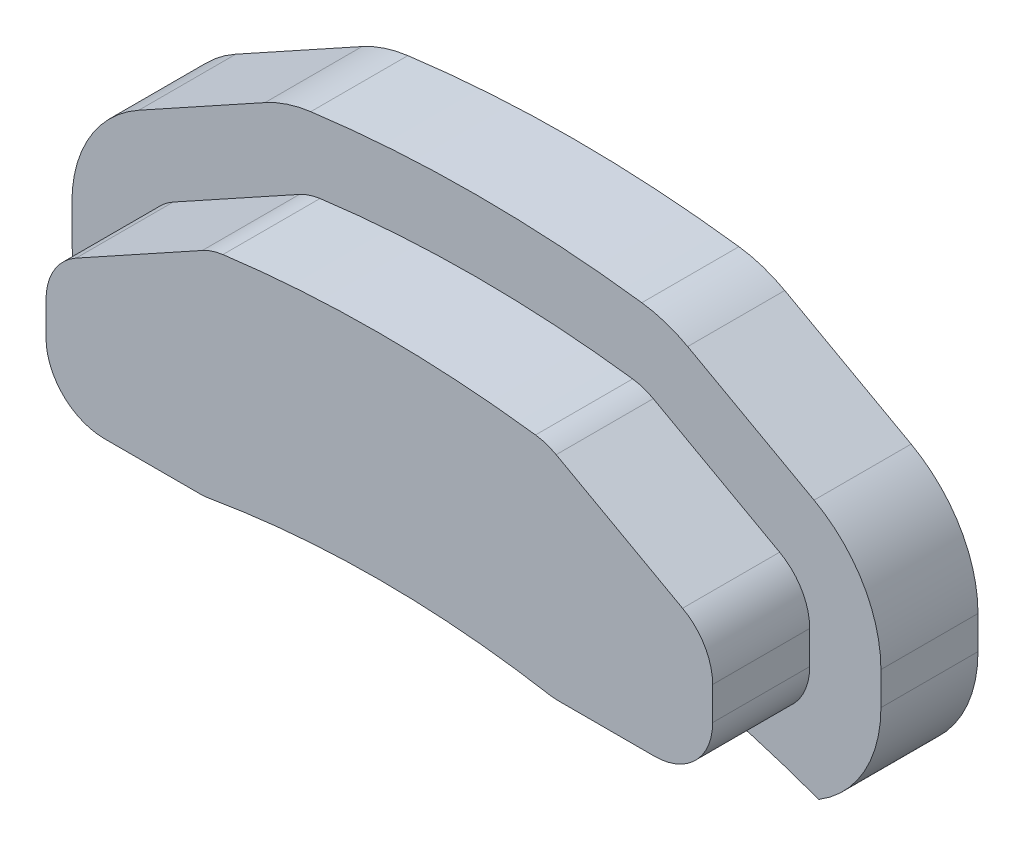
SolidWorks part; units mm, degrees
ref_plane "Front Plane" through (0, 0, 0) normal (0, 0, 1) x (1, 0, 0)
ref_plane "Top Plane" through (0, 0, 0) normal (0, 1, 0) x (1, 0, 0)
ref_plane "Right Plane" through (0, 0, 0) normal (1, 0, 0) x (0, 0, -1)
sketch "Sketch1" plane through (0, 0, 0) normal (0, 0, 1) x (1, 0, 0)
  line L0 (-5.4758, 36.7504) -> (-9.377, 34.5954)
  line L3 (-10.3066, 32) -> (-10.3066, 33.0198)
  line L8 (-5.5524, 30.2) -> (-8.5066, 30.2)
  line L9 (5.5342, 30.2) -> (8.4935, 30.2)
  line L10 (10.2935, 32) -> (10.2935, 33.0198)
  line L11 (5.4587, 36.7526) -> (9.3639, 34.5954)
  arc A0 (-9.377, 34.5954) -> (-10.3066, 33.0198) centre (-8.5066, 33.0198) ccw
  arc A17 (-8.5066, 30.2) -> (-10.3066, 32) centre (-8.5066, 32) cw
  arc A18 (-5.5524, 30.2) -> (-5.2457, 30.2263) centre (-5.5524, 32) ccw
  arc A19 (-5.2457, 30.2263) -> (-0.0091, 30.675) centre (-0.0182, 0) cw
  arc A20 (5.2274, 30.2263) -> (-0.0091, 30.675) centre (0, 0) ccw
  arc A21 (5.5342, 30.2) -> (5.2274, 30.2263) centre (5.5342, 32) cw
  arc A22 (8.4935, 30.2) -> (10.2935, 32) centre (8.4935, 32) ccw
  arc A23 (10.2935, 33.0198) -> (9.3639, 34.5954) centre (8.4935, 33.0198) ccw
  arc A24 (5.4587, 36.7526) -> (4.8212, 36.9619) centre (4.5884, 35.177) ccw
  arc A25 (4.8212, 36.9619) -> (-4.8392, 36.9595) centre (0, 0) ccw
  arc A26 (-4.8392, 36.9595) -> (-5.4758, 36.7504) centre (-4.6055, 35.1748) ccw
  point P0 (0, 0)
  point P1 (6.3862, 36.9268)
  point P3 (-5.1933, 30.0292)
  point P4 (-6.3862, 36.9268)
  point P12 (0, 0)
  point P13 (5.1933, 30.0292)
extrude "Boss-Extrude1" add sketch "Sketch1" along normal blind 5 contours A25 A26 L0 A0 L3 A17 L8 A18 A19 A20 A21 L9 A22 L10 A23 L11 A24 region at (-0.0063, 33.4615, 0)
sketch "Sketch2" plane through (0, 0, 0) normal (0, 0, -1) x (-1, 0, 0)
  line L19 (12.5066, 32) -> (12.5066, 33.0198)
  line L20 (10.4407, 36.5212) -> (6.5396, 38.6761)
  line L21 (-6.5225, 38.6783) -> (-10.4276, 36.5212)
  line L22 (-12.4935, 33.0198) -> (-12.4935, 32)
  arc A15 (0.0096, 30.475) -> (-10.5721, 28.5824) centre (0, 0) ccw
  arc A17 (0.0096, 30.475) -> (10.5913, 28.5824) centre (0.0192, 0) cw
  arc A42 (10.5802, 28.5794) -> (12.5066, 32) centre (8.5066, 32) ccw
  arc A43 (12.5066, 33.0198) -> (10.4407, 36.5212) centre (8.5066, 33.0198) ccw
  arc A44 (-5.1057, 39.1434) -> (-6.5225, 38.6783) centre (-4.5884, 35.177) ccw
  arc A45 (-10.4276, 36.5212) -> (-12.4935, 33.0198) centre (-8.4935, 33.0198) ccw
  arc A46 (-12.4935, 32) -> (-10.5721, 28.5824) centre (-8.4935, 32) ccw
  arc A52 (0.0096, 28.475) -> (0.0091, 28.475) centre (0.0182, 0) ccw
  arc A56 (6.5396, 38.6761) -> (5.1248, 39.1409) centre (4.6055, 35.1748) ccw
  arc A58 (5.1248, 39.1409) -> (-5.1057, 39.1434) centre (0, 0) ccw
extrude "Boss-Extrude2" add sketch "Sketch2" against normal up to surface (3 mm away) region at (-0.006, 34.0783, 0)
sketch "Sketch3" plane through (0, 0, 5) normal (0, 0, 1) x (1, 0, 0)
  circle A1 centre (-0.0065, 35) radius 1.75
sketch "Sketch5" plane through (0, 0, 5) normal (0, 0, 1) x (1, 0, 0)
  line L0 (0, 0) -> (0, 57.6204)
sketch "Sketch6" plane through (0, 0, 5) normal (0, 0, 1) x (1, 0, 0)
  line L6 (-5.4758, 36.7504) -> (-9.377, 34.5954)
  line L7 (-10.3066, 33.0198) -> (-10.3066, 32)
  line L8 (-8.5066, 30.2) -> (-5.5524, 30.2)
  line L9 (5.5342, 30.2) -> (8.4935, 30.2)
  line L10 (10.2935, 32) -> (10.2935, 33.0198)
  line L11 (9.3639, 34.5954) -> (5.4587, 36.7526)
  line L18 (-5.4758, 36.7504) -> (-9.377, 34.5954)
  line L19 (-10.3066, 33.0198) -> (-10.3066, 32)
  line L20 (-8.5066, 30.2) -> (-5.5524, 30.2)
  line L21 (5.5342, 30.2) -> (8.4935, 30.2)
  line L22 (10.2935, 32) -> (10.2935, 33.0198)
  line L23 (9.3639, 34.5954) -> (5.4587, 36.7526)
  arc A11 (4.8212, 36.9619) -> (-4.8392, 36.9595) centre (0, 0) ccw
  arc A12 (-4.8392, 36.9595) -> (-5.4758, 36.7504) centre (-4.6055, 35.1748) ccw
  arc A13 (-9.377, 34.5954) -> (-10.3066, 33.0198) centre (-8.5066, 33.0198) ccw
  arc A14 (-10.3066, 32) -> (-8.5066, 30.2) centre (-8.5066, 32) ccw
  arc A15 (-5.5524, 30.2) -> (-5.2457, 30.2263) centre (-5.5524, 32) ccw
  arc A16 (-0.0091, 30.675) -> (-5.2457, 30.2263) centre (-0.0182, 0) ccw
  arc A17 (5.2274, 30.2263) -> (-0.0091, 30.675) centre (0, 0) ccw
  arc A18 (5.2274, 30.2263) -> (5.5342, 30.2) centre (5.5342, 32) ccw
  arc A19 (8.4935, 30.2) -> (10.2935, 32) centre (8.4935, 32) ccw
  arc A20 (10.2935, 33.0198) -> (9.3639, 34.5954) centre (8.4935, 33.0198) ccw
  arc A21 (5.4587, 36.7526) -> (4.8212, 36.9619) centre (4.5884, 35.177) ccw
  arc A33 (4.8212, 36.9619) -> (-4.8392, 36.9595) centre (0, 0) ccw
  arc A34 (-4.8392, 36.9595) -> (-5.4758, 36.7504) centre (-4.6055, 35.1748) ccw
  arc A35 (-9.377, 34.5954) -> (-10.3066, 33.0198) centre (-8.5066, 33.0198) ccw
  arc A36 (-10.3066, 32) -> (-8.5066, 30.2) centre (-8.5066, 32) ccw
  arc A37 (-5.5524, 30.2) -> (-5.2457, 30.2263) centre (-5.5524, 32) ccw
  arc A38 (-0.0091, 30.675) -> (-5.2457, 30.2263) centre (-0.0182, 0) ccw
  arc A39 (5.2274, 30.2263) -> (-0.0091, 30.675) centre (0, 0) ccw
  arc A40 (5.2274, 30.2263) -> (5.5342, 30.2) centre (5.5342, 32) ccw
  arc A41 (8.4935, 30.2) -> (10.2935, 32) centre (8.4935, 32) ccw
  arc A42 (10.2935, 33.0198) -> (9.3639, 34.5954) centre (8.4935, 33.0198) ccw
  arc A43 (5.4587, 36.7526) -> (4.8212, 36.9619) centre (4.5884, 35.177) ccw
  dimension "D1" = 0
extrude "Boss-Extrude3" add sketch "Sketch6" along normal blind 1
